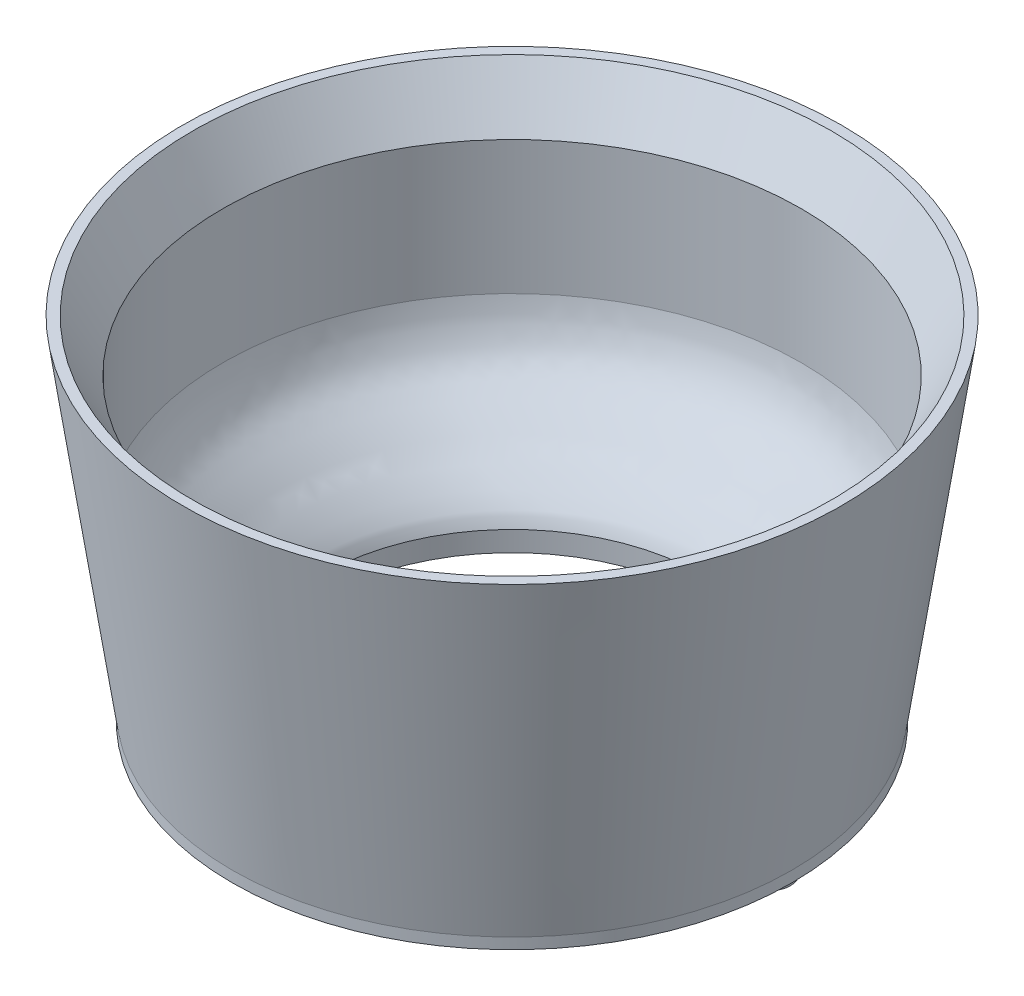
SolidWorks part; units mm, degrees
material "ABS PC"
ref_plane "Front Plane" through (0, 0, 0) normal (0, 0, 1) x (1, 0, 0)
ref_plane "Top Plane" through (0, 0, 0) normal (0, 1, 0) x (1, 0, 0)
ref_plane "Right Plane" through (0, 0, 0) normal (1, 0, 0) x (0, 0, -1)
sketch "Sketch1" plane through (0, 0, 0) normal (1, 0, 0) x (0, 0, -1)
  line L0 (26.0878, 274.978) -> (26.0878, 232.1195)
  line L2 (40.135, 299.274) -> (-40.135, 299.274) construction
  line L5 (0, 324) -> (3.2968, 324)
  line L8 (0, 324) -> (0, 0) construction
  line L9 (26.0878, 262.3641) -> (26.0878, 259.4973) construction
  line L12 (40.135, 302.9291) -> (40.135, 295.6188)
  line L16 (0, 0) -> (51.9362, 327.9125) construction
  line L17 (0, 324) -> (0, 332) construction
  line L18 (26.0878, 274.978) -> (26.0878, 268.978) construction
  line L19 (26.0878, 268.978) -> (26.0878, 248.978) construction
  line L20 (26.0878, 268.978) -> (42.6019, 268.978) construction
  line L21 (26.0878, 274.978) -> (43.5522, 274.978) construction
  line L22 (26.0878, 248.978) -> (39.4342, 248.978) construction
  line L23 (0, 0) -> (-51.9362, 327.9125) construction
  line L24 (-47.4003, 299.274) -> (-47.4003, 268.978) construction
  line L25 (-47.4003, 268.978) -> (-42.6019, 268.978) construction
  line L26 (0, 332) -> (0, 76.96) construction
  line L27 (0, 76.96) -> (400, 76.96) construction
  line L28 (0, 76.96) -> (-400, 76.96) construction
  line L29 (-200, 76.96) -> (-200, 183.96) construction
  line L30 (200, 76.96) -> (200, 183.96) construction
  line L31 (-200, 183.96) -> (-200, 182.57) construction
  line L32 (-200, 182.57) -> (400, 182.57) construction
  line L33 (-200, 182.57) -> (-400, 182.57) construction
  line L38 (0, 186.1152) -> (0, 324)
  line L39 (26.0878, 232.1195) -> (26.0878, 182.57) construction
  line L41 (21.6442, 226.0993) -> (26.0878, 226.0993)
  line L42 (26.0878, 226.0993) -> (26.0878, 186.1152)
  line L43 (26.0878, 186.1152) -> (0, 186.1152)
  line L44 (0, 0) -> (575.122, 0) construction
  arc A0 (-298.7691, 144.7791) -> (305.6579, 129.6043) centre (0, 0) cw construction
  spline S0 degree 3 poles (21.6442, 226.0993) (21.9584, 226.1509) (22.4049, 226.153) (22.896, 226.3321) (23.44, 226.7494) (24.2443, 227.2014) (25.0066, 227.9724) (25.5796, 228.9522) (25.8622, 230.393) (26.0228, 231.4436) (26.0878, 232.1195) knots 0 0 0 0 0.091924 0.112491 0.205673 0.333714 0.459267 0.602423 0.748839 1 1 1 1
  spline S1 degree 3 poles (3.2968, 324) (4.1972, 323.8396) (5.699, 323.816) (7.6935, 323.4297) (9.2722, 323.1563) (10.7507, 322.8538) (12.1816, 322.5577) (13.6372, 322.313) (14.8643, 321.9117) (15.9115, 321.5662) (16.81, 321.2491) (17.7339, 321.0149) (18.8379, 320.6416) (19.931, 320.1935) (21.0686, 319.6948) (22.141, 319.2627) (23.2156, 318.6856) (24.4371, 318.1163) (25.6762, 317.3518) (27.1066, 316.7518) (28.4318, 315.7832) (29.7322, 314.8939) (31.058, 313.93) (32.1959, 312.8581) (33.3378, 311.8503) (34.4539, 310.9646) (35.3895, 309.8867) (36.5078, 309.0949) (37.2942, 308.0208) (38.1233, 307.1238) (38.9048, 306.0961) (39.4724, 304.6349) (40.2774, 303.734) (40.135, 302.9291) knots 0 0 0 0 0.061585 0.100795 0.136831 0.1697 0.202569 0.235438 0.269088 0.289473 0.309858 0.333319 0.353706 0.388423 0.412965 0.437514 0.46634 0.495168 0.528354 0.564387 0.59925 0.638593 0.670824 0.709635 0.743897 0.773612 0.805519 0.839783 0.864953 0.89467 0.922395 0.951224 1 1 1 1
  spline S2 degree 3 poles (40.135, 295.6188) (39.9636, 294.7131) (39.7869, 293.3689) (39.1095, 291.6901) (38.6019, 290.4599) (37.8418, 289.2392) (36.9195, 288.2279) (35.9232, 287.2651) (34.974, 286.2515) (33.8311, 285.3463) (32.8233, 284.2966) (31.8701, 283.2868) (30.7668, 282.4387) (29.8742, 281.4644) (28.8604, 280.5152) (28.0567, 279.5119) (27.1438, 278.5569) (26.4968, 277.0287) (26.0081, 275.8567) (26.0878, 274.978) knots 0 0 0 0 0.108356 0.15601 0.210945 0.263562 0.322855 0.370186 0.4254 0.484692 0.539909 0.595126 0.646549 0.701764 0.749093 0.808384 0.85195 0.901837 1 1 1 1
  point P10 (0, 299.274)
  point P63 (0, 299.274)
  dimension "D3" = 9
  dimension "D1" = 40.135
  dimension "D2" = 324
  dimension "D4" = 8
  dimension "D5" = 3.2968
  dimension "D6" = 4.4435
  dimension "D7" = 6.0202
  dimension "D8" = 7.7403
  dimension "D9" = 6
  dimension "D10" = 20
  dimension "D11" = 9.317
  dimension "D12" = 10.7504
  dimension "D13" = 255.04
  dimension "D14" = 107
  dimension "D15" = 107
  dimension "D16" = 332
  dimension "D17" = 105.61
  dimension "D18" = 105.61
  dimension "D19" = 12.1838
  dimension "D20" = 13.6172
  dimension "D21" = 15.0506
  dimension "D22" = 15.9106
  dimension "D23" = 16.7707
  dimension "D24" = 17.7739
  dimension "D25" = 18.6341
  dimension "D26" = 20.0676
  dimension "D27" = 21.0708
  dimension "D28" = 22.0743
  dimension "D29" = 23.2209
  dimension "D30" = 24.3677
  dimension "D31" = 25.6578
  dimension "D32" = 27.0911
  dimension "D33" = 28.3811
  dimension "D34" = 29.8146
  dimension "D35" = 30.9613
  dimension "D36" = 32.2513
  dimension "D37" = 33.3981
  dimension "D38" = 34.4014
  dimension "D39" = 35.4048
  dimension "D40" = 36.5516
  dimension "D41" = 37.2681
  dimension "D42" = 38.1282
  dimension "D43" = 38.8449
  dimension "D44" = 39.4183
  dimension "D45" = 39.9917
  dimension "D46" = 323.8567
  dimension "D47" = 323.7133
  dimension "D48" = 323.4267
  dimension "D49" = 323.1399
  dimension "D50" = 322.8533
  dimension "D51" = 322.5666
  dimension "D52" = 322.2799
  dimension "D53" = 321.8499
  dimension "D54" = 321.5632
  dimension "D55" = 321.2765
  dimension "D56" = 320.9899
  dimension "D57" = 320.7031
  dimension "D58" = 320.1297
  dimension "D59" = 319.6998
  dimension "D60" = 319.2698
  dimension "D61" = 318.6965
  dimension "D62" = 318.1231
  dimension "D63" = 317.4064
  dimension "D64" = 316.6897
  dimension "D65" = 315.8296
  dimension "D66" = 314.8263
  dimension "D67" = 313.9663
  dimension "D68" = 312.8195
  dimension "D69" = 311.8162
  dimension "D70" = 310.9562
  dimension "D71" = 309.9528
  dimension "D72" = 308.9493
  dimension "D73" = 308.0893
  dimension "D74" = 307.086
  dimension "D75" = 306.0826
  dimension "D76" = 304.9359
  dimension "D77" = 303.9325
  dimension "D78" = 302.9291
sketch "Sketch2" plane through (0, 0, 0) normal (1, 0, 0) x (0, 0, -1)
  line L0 (0, 324) -> (3.2968, 324) construction
  line L1 (26.5078, 274.997) -> (26.5078, 273.8486)
  line L2 (40.5477, 295.5407) -> (40.5477, 314.2386)
  line L3 (40.135, 295.6188) -> (40.135, 302.9302) construction
  line L4 (40.135, 295.6188) -> (26.0878, 274.978) construction
  line L5 (0, 324.42) -> (3.4084, 324.42) construction
  line L6 (3.2968, 324) -> (40.135, 302.9302) construction
  line L7 (3.4084, 324.42) -> (40.555, 303.1738) construction
  line L8 (26.0878, 274.978) -> (26.0878, 232.1195) construction
  line L9 (40.555, 295.4895) -> (26.435, 274.7417) construction
  line L10 (0, 5) -> (0, 407.9498) construction
  line L12 (26.5078, 273.8486) -> (38.5078, 273.8486) construction
  line L13 (26.5078, 274.997) -> (26.5078, 232.1195) construction
  line L14 (38.5078, 273.8486) -> (45.76, 323.5611) construction
  line L17 (40.5477, 314.2386) -> (45.93, 323.5611) construction
  line L18 (45.93, 323.5611) -> (45.76, 323.5611) construction
  line L19 (0, 186.1152) -> (0, 324) construction
  line L20 (0, 324) -> (0, 332) construction
  line L21 (40.555, 295.4895) -> (40.555, 303.1738) construction
  line L22 (0, 5) -> (47.1644, 328.2999) construction
  line L23 (45.93, 323.5611) -> (46.473, 323.5611) construction
  line L24 (46.473, 323.5611) -> (39.2208, 273.8486) construction
  line L25 (39.2208, 273.8486) -> (26.5078, 273.8486)
  line L26 (44.7753, 321.5611) -> (46.1813, 321.5611)
  line L27 (44.7753, 321.5611) -> (40.5477, 314.2386)
  line L28 (46.1813, 321.5611) -> (39.2208, 273.8486)
  spline S0 degree 1 poles (40.5477, 295.5407) (26.5078, 274.997) knots 0 0 1 1 construction
  spline S1 degree 3 poles (40.135, 295.6188) (39.9636, 294.7131) (39.7869, 293.3689) (39.1095, 291.6901) (38.6019, 290.4599) (37.8418, 289.2392) (36.9195, 288.2279) (35.9232, 287.2651) (34.974, 286.2515) (33.8311, 285.3463) (32.8233, 284.2966) (31.8701, 283.2868) (30.7668, 282.4387) (29.8742, 281.4644) (28.8604, 280.5152) (28.0567, 279.5119) (27.1438, 278.5569) (26.4968, 277.0287) (26.0081, 275.8567) (26.0878, 274.978) knots 0 0 0 0 0.108356 0.15601 0.210945 0.263562 0.322855 0.370186 0.4254 0.484692 0.539909 0.595126 0.646549 0.701764 0.749093 0.808384 0.85195 0.901837 1 1 1 1 construction
  spline S2 degree 3 poles (40.5477, 295.5407) (40.4477, 295.0127) (40.2928, 293.9708) (39.9309, 292.5875) (39.5162, 291.5815) (39.1084, 290.578) (38.4397, 289.317) (37.3314, 288.0326) (36.3684, 287.1154) (35.6302, 286.3401) (35.0165, 285.7627) (34.3943, 285.2472) (33.6355, 284.5566) (32.9204, 283.7714) (32.1297, 282.9861) (31.4852, 282.4595) (30.915, 281.9635) (30.3717, 281.3913) (29.7828, 280.8046) (29.2276, 280.2622) (28.7248, 279.6749) (28.1804, 279.0397) (27.6518, 278.4702) (27.3081, 277.8768) (26.9952, 277.1272) (26.598, 276.1645) (26.4648, 275.4705) (26.5078, 274.997) knots 0 0 0 0 0.062544 0.125088 0.15636 0.187632 0.250176 0.31272 0.375264 0.406536 0.437808 0.46908 0.500352 0.562896 0.594168 0.62544 0.656713 0.687985 0.719257 0.750529 0.781801 0.813073 0.844345 0.875617 0.906889 0.938161 1.000705 1.000705 1.000705 1.000705
  point P38 (0, 328)
  dimension "D4" = 1.1484
  dimension "D5" = 8.3
  dimension "D6" = 30
  dimension "D7" = 45.93
  dimension "D8" = 40.39
  dimension "D9" = 8.3
  dimension "D10" = 40.5477
  dimension "D3" = 12
  dimension "D11" = 18.6979
  dimension "D12" = 2
  dimension "D13" = 5
  dimension "D1" = 0.42
  dimension "D2" = 0.42
revolve "Revolve6" add sketch "Sketch2" angle 360 about L10
sketch "Sketch3" plane through (0, 0, 0) normal (1, 0, 0) x (0, 0, -1)
  line L0 (44.1979, 321.5611) -> (40.5477, 314.2386) construction
  line L3 (46.1813, 321.5611) -> (-46.1813, 321.5611) construction
  line L4 (44.7753, 321.5611) -> (-44.7753, 321.5611) construction
  line L5 (40.5477, 314.2386) -> (-40.5477, 314.2386) construction
  line L6 (40.5477, 314.2386) -> (54.812, 333.8718)
  line L8 (54.812, 333.8718) -> (54.812, 347.837)
  line L9 (54.812, 347.837) -> (0, 347.837)
  line L10 (0, 347.837) -> (0, 311.6751)
  line L11 (0, 186.1152) -> (0, 324) construction
  line L12 (0, 311.6751) -> (40.5477, 311.6751)
  line L13 (40.5477, 311.6751) -> (40.5477, 314.2386)
  dimension "D1" = 36
  dimension "D2" = 54.812
revolve "Cut-Revolve1" [suppressed] cut sketch "Sketch3" angle 360 about L10
sketch "Sketch4" plane through (0, 273.8486, 0) normal (0, -1, 0) x (1, 0, 0)
  line L0 (0, 0) -> (36, 0) construction
  line L1 (0, 0) -> (-31.1769, 18) construction
  circle A0 centre (0, 0) radius 36 construction
  circle A1 centre (-31.1769, 18) radius 3
  circle A2 centre (36, 0) radius 3
  dimension "D1" = 72
  dimension "D3" = 6
  dimension "D4" = 6
  dimension "D2" = 150
extrude "Boss-Extrude1" add sketch "Sketch4" along normal blind 2
sketch "Sketch5" [suppressed] plane through (0, 263.8486, 0) normal (0, -1, 0) x (1, 0, 0)
  circle A0 centre (36, 0) radius 3.175
  circle A1 centre (-31.1769, 18) radius 3.175
  dimension "D1" = 6.35
  dimension "D2" = 6.35
extrude "Boss-Extrude2" [suppressed] add sketch "Sketch5" along normal blind 5
chamfer "Chamfer2" [suppressed] distance 9 angle 4
sketch "Sketch7" plane through (0, 0, 0) normal (1, 0, 0) x (0, 0, -1)
  line L0 (0, 5) -> (0, 407.9498) construction
  line L1 (26.5078, 273.8486) -> (39.2208, 273.8486) construction
  line L2 (39.2208, 273.8486) -> (39.2208, 272.3194)
  line L4 (26.5078, 273.8486) -> (26.5078, 274.3486)
  line L5 (26.5078, 274.3486) -> (39.2208, 274.3486)
  line L6 (39.2208, 274.3486) -> (39.2208, 273.8486)
  circle A0 centre (0, -0.122) radius 275.25 construction
  arc A1 (39.2208, 272.3194) -> (26.5078, 273.8486) centre (0, -0.122) ccw
  dimension "D1" = 550.5
  dimension "D2" = 0.5
revolve "Revolve7" add sketch "Sketch7" angle 360 about L10
sketch "Sketch9" plane through (0, 271.8486, 0) normal (0, -1, 0) x (1, 0, 0)
  circle A0 centre (36, 0) radius 1.5
  circle A1 centre (-31.1769, 18) radius 1.5
  dimension "D1" = 3
  dimension "D2" = 3
extrude "Cut-Extrude1" cut sketch "Sketch9" against normal blind 6
sketch "Sketch10" plane through (0, 271.8486, 0) normal (0, -1, 0) x (1, 0, 0)
  circle A0 centre (36, 0) radius 2
  circle A1 centre (-31.1769, 18) radius 2
  dimension "D1" = 4
  dimension "D2" = 4
extrude "Cut-Extrude2" cut sketch "Sketch10" against normal blind 0.5
chamfer "Chamfer3" distance 0.55 angle 45 2 edges at (36, 271.8486, -2) (-31.1769, 271.8486, 16)
sketch "Sketch11" plane through (0, 321.5611, 0) normal (0, 1, 0) x (1, 0, 0)
  circle A0 centre (0, 0) radius 26.8
  dimension "D1" = 53.6
extrude "Cut-Extrude3" cut sketch "Sketch11" against normal through all
